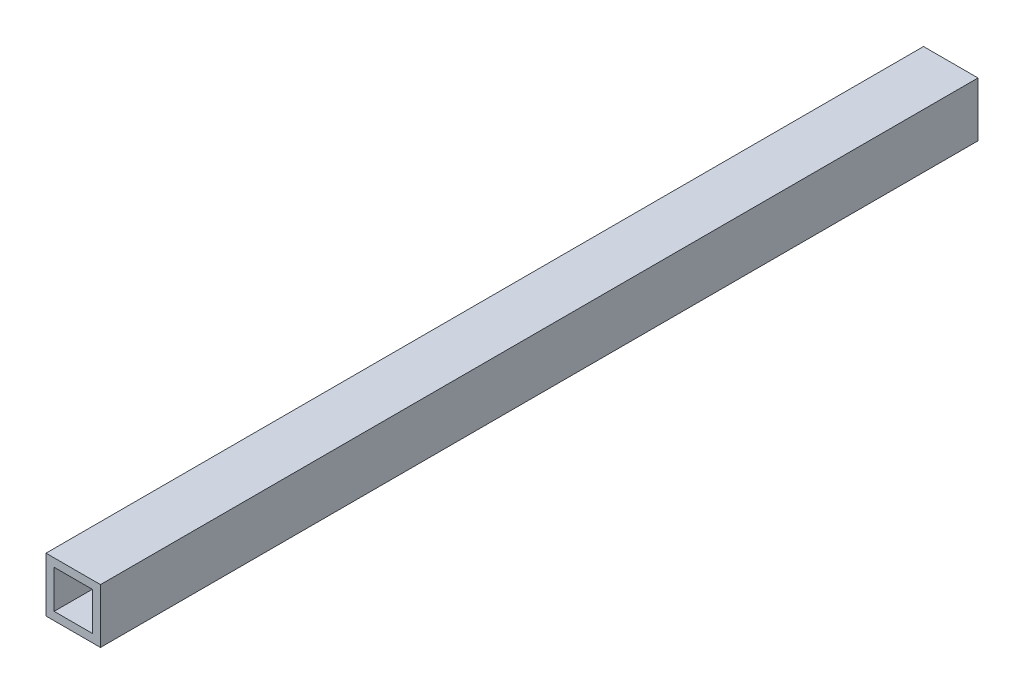
SolidWorks part; units mm, degrees
ref_plane "Plan de face" through (0, 0, 0) normal (0, 0, 1) x (1, 0, 0)
ref_plane "Plan de dessus" through (0, 0, 0) normal (0, 1, 0) x (1, 0, 0)
ref_plane "Plan de droite" through (0, 0, 0) normal (1, 0, 0) x (0, 0, -1)
sketch "Esquisse1" plane through (0, 0, 0) normal (0, 0, 1) x (1, 0, 0)
  line L1 (0, 0) -> (11.7, 0)
  line L2 (0, 0) -> (0, 11.7)
  line L3 (0, 11.7) -> (11.7, 11.7)
  line L4 (11.7, 0) -> (11.7, 11.7)
  line L5 (1.75, 1.75) -> (9.95, 1.75)
  line L6 (1.75, 1.75) -> (1.75, 9.95)
  line L7 (1.75, 9.95) -> (9.95, 9.95)
  line L8 (9.95, 1.75) -> (9.95, 9.95)
  dimension "D1" = 11.7
  dimension "D2" = 11.7
  dimension "D3" = 8.2
  dimension "D4" = 8.2
  dimension "D5" = 1.75
  dimension "D6" = 1.75
  dimension "D7" = 1.75
extrude "Boss.-Extru.1" add sketch "Esquisse1" along normal blind 188.5
